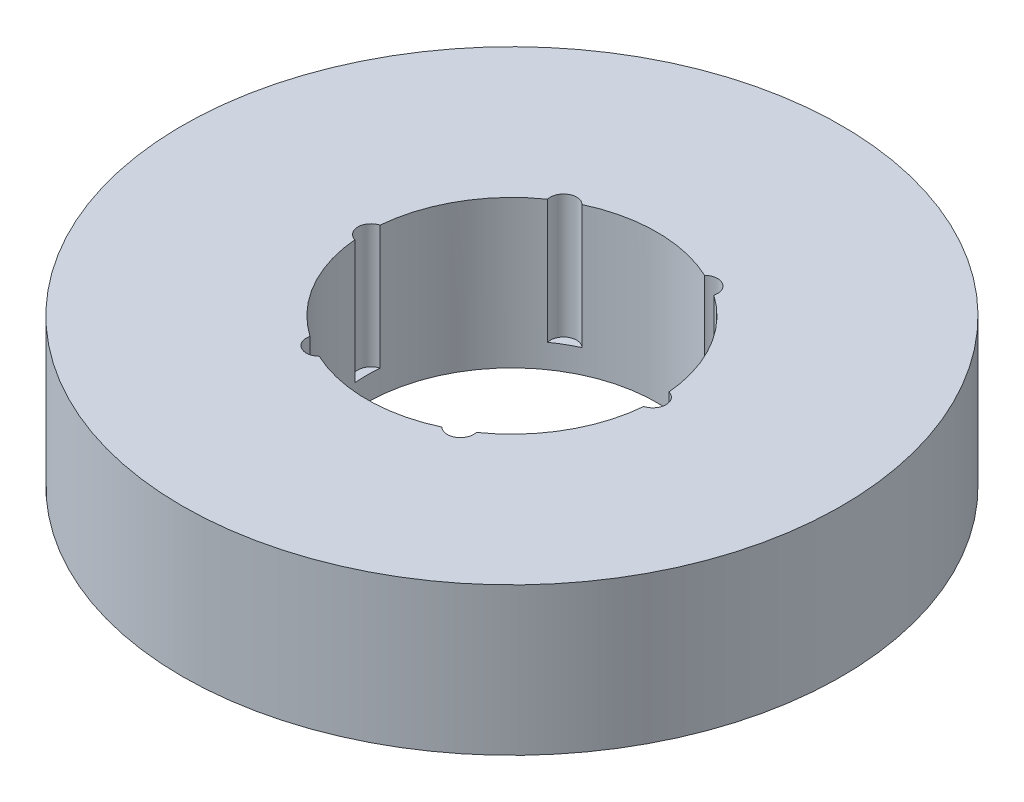
SolidWorks part; units mm, degrees
ref_plane "Front Plane" through (0, 0, 0) normal (0, 0, 1) x (1, 0, 0)
ref_plane "Top Plane" through (0, 0, 0) normal (0, 1, 0) x (1, 0, 0)
ref_plane "Right Plane" through (0, 0, 0) normal (1, 0, 0) x (0, 0, -1)
sketch "Sketch1" plane through (0, 0, 0) normal (0, 1, 0) x (1, 0, 0)
  circle A0 centre (0, 0) radius 62.5
  dimension "FLANGE_OD" = 125
extrude "Boss-Extrude1" add sketch "Sketch1" along normal blind 28
sketch "Sketch2" plane through (0, 0, 0) normal (0, 1, 0) x (1, 0, 0)
  circle A0 centre (0, 0) radius 27.5
  dimension "BORE_D" = 55
extrude "Cut-Extrude1" cut sketch "Sketch2" along normal through all
sketch "Sketch3" plane through (0, 28, 0) normal (0, 1, 0) x (1, 0, 0)
  circle A0 centre (0, 0) radius 26.7241 construction
  circle A1 centre (-26.7241, 0) radius 2.4846
  dimension "BOLT_D" = 4.9691
  dimension "BOLT_PCD" = 53.4482
extrude "Cut-Extrude2" cut sketch "Sketch3" against normal blind 23.4959
pattern_circular "CirPattern1" count 6 over 360 about axis through (0, 0, 0) along (0, 1, 0) of "Cut-Extrude2"
